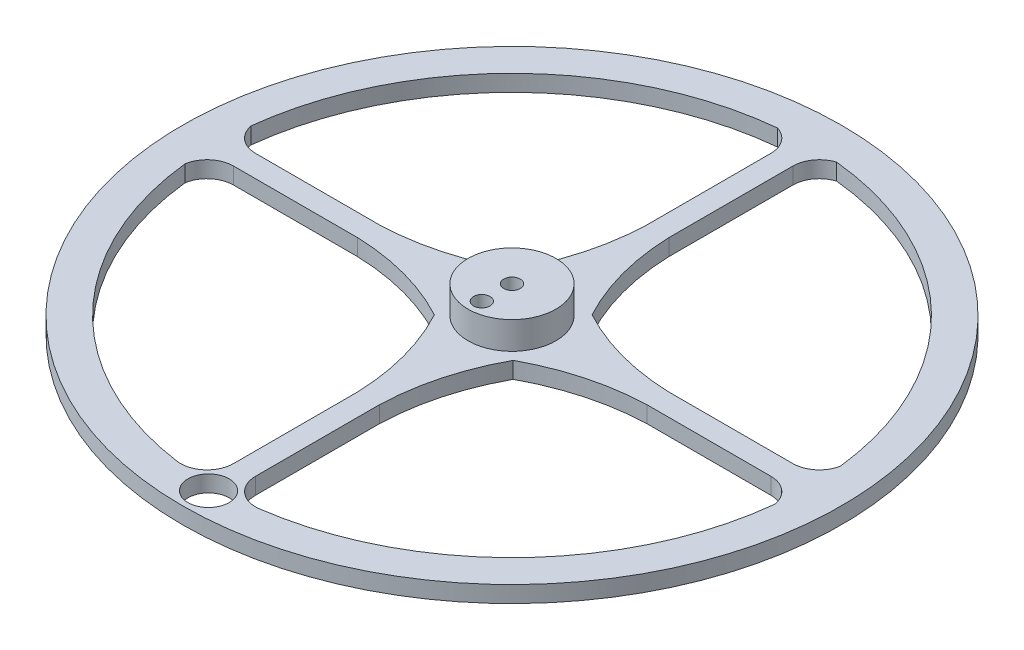
SolidWorks part; units mm, degrees
ref_plane "Front Plane" through (0, 0, 0) normal (0, 0, 1) x (1, 0, 0)
ref_plane "Top Plane" through (0, 0, 0) normal (0, 1, 0) x (1, 0, 0)
ref_plane "Right Plane" through (0, 0, 0) normal (1, 0, 0) x (0, 0, -1)
sketch "Sketch1" plane through (0, 0, 0) normal (0, 1, 0) x (1, 0, 0)
  line L0 (2, -48.6942) -> (2, -26.1095)
  line L2 (7.1789, 7.3963) -> (-7.1789, 7.3963) construction
  line L3 (-2, -26.1095) -> (-2, -48.6942)
  line L4 (-2, -26.1095) -> (2, -26.1095) construction
  line L5 (0, -9) -> (0, 9) construction
  line L6 (0, -60) -> (0, 9) construction
  line L7 (7.1789, 7.3963) -> (7.1789, -6.9616) construction
  line L8 (7.1789, -6.9616) -> (-7.1789, -6.9616) construction
  line L9 (-11.0325, 9) -> (11.0325, 9) construction
  line L10 (0, 9) -> (0, 10.5613) construction
  line L11 (-26.3268, 2.2174) -> (-48.9115, 2.2174)
  line L12 (0, -26.1095) -> (0, -9) construction
  line L13 (-7.5, -53.4766) -> (7.5, -53.4766) construction
  line L14 (0, -60) -> (0, -53.4766) construction
  line L15 (-48.9115, -1.7826) -> (-26.3268, -1.7826)
  line L16 (-60.2174, 0.2174) -> (8.7826, 0.2174) construction
  line L17 (2, 26.5442) -> (2, 49.1289)
  line L18 (-2, 49.1289) -> (-2, 26.5442)
  line L19 (0, 60.4347) -> (0, -8.5653) construction
  line L20 (26.3268, -1.7826) -> (48.9115, -1.7826)
  line L21 (48.9115, 2.2174) -> (26.3268, 2.2174)
  line L22 (60.2174, 0.2174) -> (-8.7826, 0.2174) construction
  line L23 (-7.1789, 7.3963) -> (-7.1789, -6.9616) construction
  circle A0 centre (0, 0) radius 60
  circle A1 centre (0, 0) radius 54
  circle A2 centre (0, 0) radius 8
  circle A3 centre (0, 0) radius 10 construction
  arc A5 (-2, -48.6942) -> (-7.5, -53.4766) centre (-6.8293, -48.6942) cw
  arc A6 (2, -48.6942) -> (7.5, -53.4766) centre (6.8293, -48.6942) ccw
  arc A12 (7.1789, -6.9616) -> (2, -26.1095) centre (44.7791, -27.4056) ccw
  arc A13 (-2, -26.1095) -> (-7.1789, -6.9616) centre (-45.1515, -27.5063) ccw
  arc A15 (-48.9115, -1.7826) -> (-53.694, -7.2826) centre (-48.9115, -6.6119) ccw
  arc A16 (-48.9115, 2.2174) -> (-53.694, 7.7174) centre (-48.9115, 7.0466) cw
  arc A17 (-26.3268, 2.2174) -> (-7.1789, 7.3963) centre (-27.7236, 45.3689) ccw
  arc A18 (-7.1789, -6.9616) -> (-26.3268, -1.7826) centre (-27.6229, -44.5618) ccw
  arc A19 (-2, 49.1289) -> (-7.5, 53.9113) centre (-6.8293, 49.1289) ccw
  arc A20 (2, 49.1289) -> (7.5, 53.9113) centre (6.8293, 49.1289) cw
  arc A21 (2, 26.5442) -> (7.1789, 7.3963) centre (45.1515, 27.941) ccw
  arc A22 (-7.1789, 7.3963) -> (-2, 26.5442) centre (-44.7791, 27.8403) ccw
  arc A23 (48.9115, 2.2174) -> (53.694, 7.7174) centre (48.9115, 7.0466) ccw
  arc A24 (48.9115, -1.7826) -> (53.694, -7.2826) centre (48.9115, -6.6119) cw
  arc A25 (26.3268, -1.7826) -> (7.1789, -6.9616) centre (27.7236, -44.9342) ccw
  arc A26 (7.1789, 7.3963) -> (26.3268, 2.2174) centre (27.6229, 44.9965) ccw
  point P6 (0, 0)
  point P7 (0, 0)
  point P90 (0, 0.2174)
  dimension "D1" = 6
  dimension "D5" = 16
  dimension "D9" = 120
  dimension "D6" = 20
  dimension "D2" = 69
  dimension "D4" = 4
  dimension "D7" = 4
  dimension "D10" = 15
extrude "Boss-Extrude1" add sketch "Sketch1" against normal blind 3 contours A0 A1 | A13 L3 A5 A1 A6 L0 A12 A2 | A2 region at (2.6583, 0, 53.491) region at (-58.3029, 0, 0) region at (0, 0, 0)
extrude "Boss-Extrude2" add sketch "Sketch1<3>" along normal blind 5 contours A2 region at (0, 0, 0)
sketch "Sketch1<3>" plane through (0, 0, 0) normal (0, 1, 0) x (1, 0, 0) same geometry as "Sketch1"
sketch "Sketch2" plane through (0, 5, 0) normal (0, 1, 0) x (1, 0, 0)
  circle A0 centre (0, 0) radius 1.5
  dimension "D1" = 3
extrude "Cut-Extrude1" cut sketch "Sketch2" against normal up to next
sketch "Sketch3" plane through (0, 0, 0) normal (0, 1, 0) x (1, 0, 0)
  line L0 (0, 0) -> (0, -55.25) construction
  circle A0 centre (0, -55.25) radius 3.75
  dimension "D1" = 7.5
  dimension "D2" = 55.25
extrude "Cut-Extrude2" cut sketch "Sketch3" against normal up to next
sketch "Sketch4" plane through (0, 5, 0) normal (0, 1, 0) x (1, 0, 0)
  line L0 (0, 0) -> (0, -5.5) construction
  circle A0 centre (0, -5.5) radius 1.5
  dimension "D2" = 3
  dimension "D1" = 5.5
extrude "Cut-Extrude3" cut sketch "Sketch4" against normal up to surface (5 mm away) up to face at (0, 0, 59)
